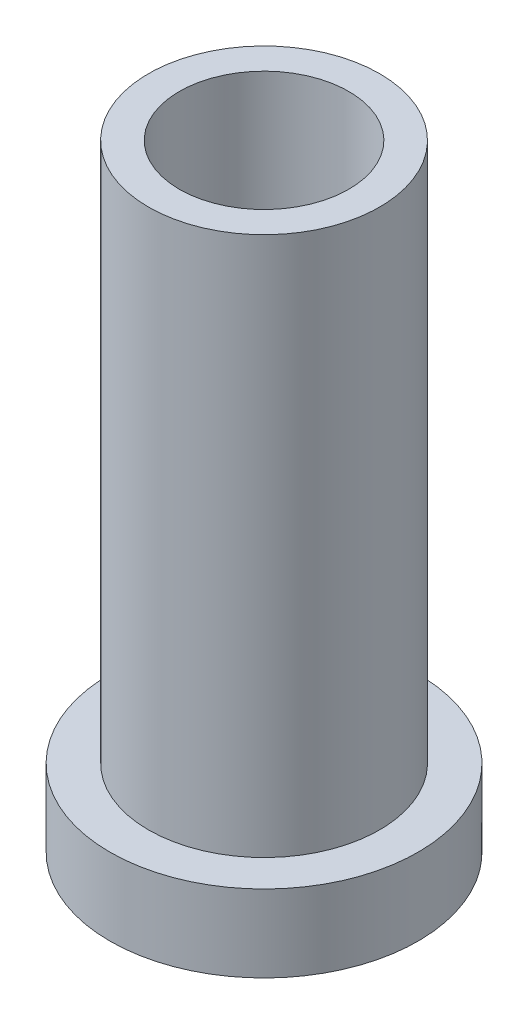
SolidWorks part; units mm, degrees
ref_plane "Front Plane" through (0, 0, 0) normal (0, 0, 1) x (1, 0, 0)
ref_plane "Top Plane" through (0, 0, 0) normal (0, 1, 0) x (1, 0, 0)
ref_plane "Right Plane" through (0, 0, 0) normal (1, 0, 0) x (0, 0, -1)
sketch "Sketch1" plane through (0, 0, 0) normal (0, 1, 0) x (1, 0, 0)
  circle A0 centre (0, 0) radius 7.5
  circle A1 centre (0, 0) radius 10
  circle A2 centre (0, 0) radius 5.5
  dimension "D1" = 20
  dimension "D2" = 15
  dimension "D3" = 11
extrude "Boss-Extrude1" add sketch "Sketch1" along normal blind 5 contours A1 A0 region at (-9.7172, 0, 0)
extrude "Boss-Extrude2" add sketch "Sketch1<3>" along normal blind 40 contours A0 A2 region at (-7.2879, 0, 0)
sketch "Sketch1<3>" plane through (0, 0, 0) normal (0, 1, 0) x (1, 0, 0) same geometry as "Sketch1"
